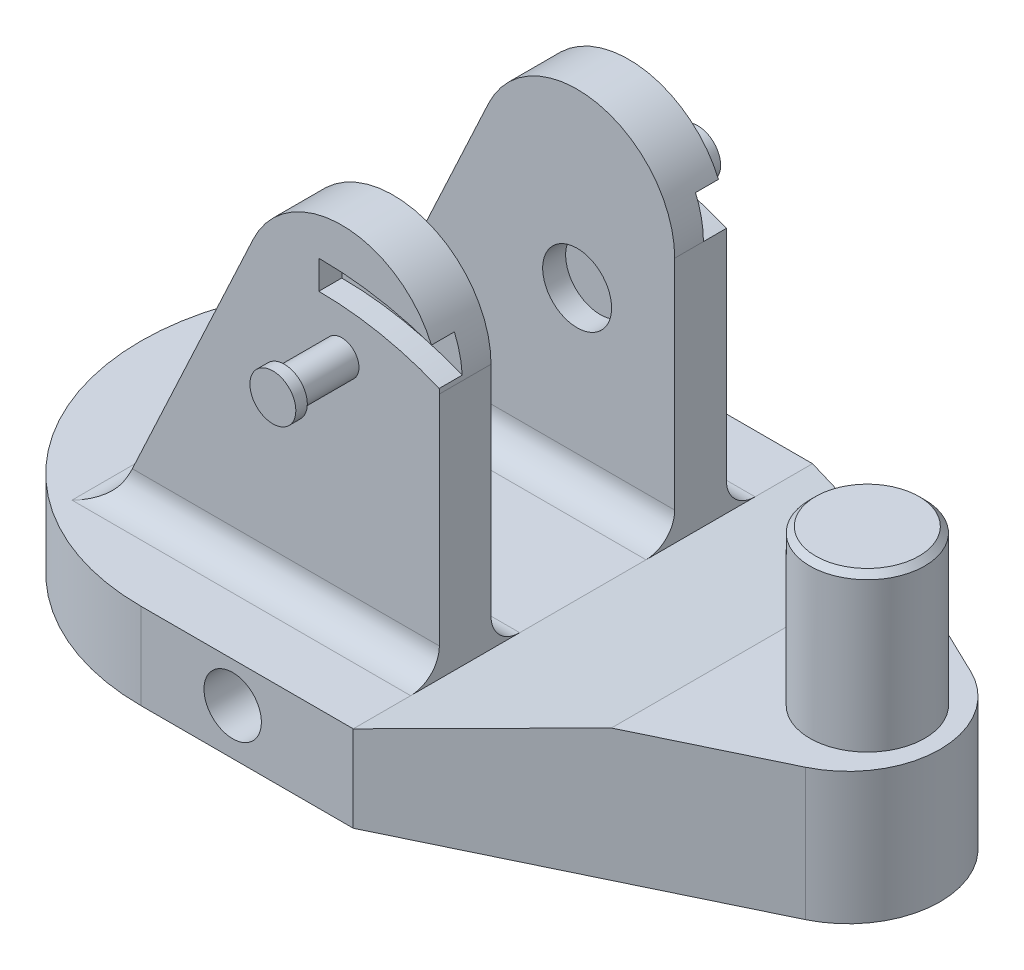
SolidWorks part; units mm, degrees
ref_plane "Płaszczyzna przednia" through (0, 0, 0) normal (0, 0, 1) x (1, 0, 0)
ref_plane "Płaszczyzna górna" through (0, 0, 0) normal (0, 1, 0) x (1, 0, 0)
ref_plane "Płaszczyzna prawa" through (0, 0, 0) normal (1, 0, 0) x (0, 0, -1)
sketch "Szkic5" plane through (0, 0, 0) normal (0, 1, 0) x (1, 0, 0)
  line L0 (0, 36.575) -> (0, -43.425) construction
  line L1 (0, -43.425) -> (37, -43.425)
  line L2 (37, -43.425) -> (37, 36.575)
  line L3 (37, 36.575) -> (0, 36.575)
  arc A0 (0, -43.425) -> (0, 36.575) centre (0, -3.425) cw
  dimension "D1" = 77
  dimension "D2" = 80
extrude "Dodanie-wyciągnięcie3" add sketch "Szkic5" along normal blind 15
sketch "Szkic7" plane through (0, 0, 0) normal (0, 1, 0) x (1, 0, 0)
  line L0 (0, 0) -> (37, 0) construction
  line L1 (37, -43.425) -> (90.1571, -17.8422)
  line L2 (37, 36.575) -> (90.1571, 10.9922)
  line L3 (0, -43.425) -> (37, -43.425) construction
  line L4 (37, -43.425) -> (37, 36.575) construction
  line L8 (0, -43.425) -> (37, -43.425)
  line L9 (37, -43.425) -> (37, 36.575)
  line L10 (37, 36.575) -> (0, 36.575)
  line L12 (37, -43.425) -> (37, 36.575)
  arc A0 (90.1571, 10.9922) -> (90.1571, -17.8422) centre (83.2185, -3.425) cw
  arc A2 (0, 36.575) -> (0, -43.425) centre (0, -3.425) ccw
  dimension "D2" = 16
  dimension "D3" = 0
  dimension "D1" = 25.7
extrude "Dodanie-wyciągnięcie4" add sketch "Szkic7" along normal blind 23
ref_plane "Płaszczyzna1" through (0, 0, 28.425) normal (0, 0, 1) x (1, 0, 0)
sketch "Szkic8" plane through (0, 0, 28.425) normal (0, 0, 1) x (1, 0, 0)
  line L0 (37, 15.0945) -> (37, 58)
  line L1 (4.5928, 65.1845) -> (-18.8087, 15)
  line L2 (0, 15) -> (37, 15) construction
  line L3 (0, 0) -> (37, 0) construction
  line L4 (0, 15) -> (-40, 15) construction
  line L5 (20, 58) -> (20, 81.5581) construction
  line L6 (20, 81.5581) -> (20, -13.5483) construction
  line L12 (0, 0) -> (37, 0)
  line L13 (37, 0) -> (37, 15)
  line L14 (37, 15) -> (0, 15)
  line L15 (0, 15) -> (0, 0)
  line L17 (37, 15.0945) -> (37, 15)
  line L18 (37, 15) -> (-18.8087, 15)
  arc A0 (37, 58) -> (4.5928, 65.1845) centre (20, 58) ccw
  dimension "D3" = 0
  dimension "D1" = 75
  dimension "D2" = 65
extrude "Dodanie-wyciągnięcie5" add sketch "Szkic8" against normal blind 9
ref_plane "Płaszczyzna4" through (0, 0, -21.575) normal (0, 0, 1) x (1, 0, 0)
sketch "Szkic23" plane through (0, 0, -21.575) normal (0, 0, 1) x (1, 0, 0)
  line L0 (37, 15) -> (37, 58)
  line L1 (37, 15) -> (-18.8087, 15)
  line L2 (-18.8087, 15) -> (4.5928, 65.1845)
  arc A0 (4.5928, 65.1845) -> (37, 58) centre (20, 58) cw
extrude "Dodanie-wyciągnięcie7" add sketch "Szkic23" along normal blind 9
sketch "Szkic24" plane through (0, 0, 28.425) normal (0, 0, 1) x (1, 0, 0)
  line L0 (37, 15) -> (67.3646, 23)
  line L1 (37, 23) -> (90.1571, 23) construction
  line L2 (67.3646, 23) -> (37, 23)
  line L3 (37, 23) -> (37, 15)
  dimension "D1" = 75.24
extrude "Wytnij-wyciągnięcie1" cut sketch "Szkic24" against normal through all both and the other way through all
sketch "Szkic26" plane through (0, 0, 19.425) normal (0, 0, -1) x (-1, 0, 0)
  line L0 (-37, 15) -> (-37, 58) construction
  line L1 (18.8087, 15) -> (-37, 15) construction
  circle A0 centre (-20, 45) radius 6
  dimension "D1" = 12
  dimension "D2" = 17
  dimension "D3" = 30
extrude "Wytnij-wyciągnięcie2" cut sketch "Szkic26" against normal blind 4
sketch "Szkic27" plane through (0, 0, -12.575) normal (0, 0, 1) x (1, 0, 0)
  line L0 (37, 15) -> (37, 58) construction
  line L1 (-18.8087, 15) -> (37, 15) construction
  circle A0 centre (20, 45) radius 6
  dimension "D1" = 12
  dimension "D2" = 17
  dimension "D3" = 30
extrude "Wytnij-wyciągnięcie3" cut sketch "Szkic27" against normal blind 4
sketch "Szkic28" plane through (0, 0, 43.425) normal (0, 0, 1) x (1, 0, 0)
  line L0 (0, 0) -> (37, 0) construction
  line L1 (-40, 15) -> (-40, 0) construction
  circle A0 centre (16, 8) radius 5
  dimension "D1" = 10
  dimension "D2" = 8
  dimension "D3" = 56
extrude "Wytnij-wyciągnięcie4" cut sketch "Szkic28" against normal through all
sketch "Szkic29" plane through (0, 23, 0) normal (0, 1, 0) x (1, 0, 0)
  circle A0 centre (86.22, -3.0978) radius 10
  arc A1 (0, 36.575) -> (0, -43.425) centre (0, -3.425) ccw construction
  arc A2 (90.1571, -17.8422) -> (90.1571, 10.9922) centre (83.2185, -3.425) ccw construction
  dimension "D1" = 20
  dimension "D2" = 126.22
extrude "Dodanie-wyciągnięcie8" add sketch "Szkic29" along normal blind 27
chamfer "Sfazowanie2" distance 1 angle 45 1 edges at (86.22, 50, 13.0978)
sketch "Szkic30" plane through (0, 0, -21.575) normal (0, 0, -1) x (-1, 0, 0)
  line L0 (-16, 8) -> (-16, 84.9488) construction
sketch "Szkic31" plane through (0, 0, 28.425) normal (0, 0, 1) x (1, 0, 0)
  line L0 (16, 8) -> (16, 84.9488) construction
  line L1 (37, 15) -> (37, 58) construction
  line L2 (-18.8087, 15) -> (37, 15) construction
  circle A0 centre (20, 55) radius 3
  dimension "D1" = 17
  dimension "D2" = 40
  dimension "D3" = 6
extrude "Dodanie-wyciągnięcie9" add sketch "Szkic31" along normal blind 10
sketch "Szkic32" plane through (0, 0, 38.425) normal (0, 0, 1) x (1, 0, 0)
  circle A0 centre (20, 55) radius 4
  dimension "D1" = 8
extrude "Dodanie-wyciągnięcie10" add sketch "Szkic32" along normal blind 2
sketch "Szkic33" plane through (0, 0, -21.575) normal (0, 0, -1) x (-1, 0, 0)
  line L0 (-37, 15) -> (-37, 58) construction
  line L1 (18.8087, 15) -> (-37, 15) construction
  circle A0 centre (-20, 55) radius 3
  dimension "D3" = 6
  dimension "D1" = 17
  dimension "D2" = 40
extrude "Dodanie-wyciągnięcie11" add sketch "Szkic33" along normal blind 10
sketch "Szkic34" plane through (0, 0, -31.575) normal (0, 0, -1) x (-1, 0, 0)
  circle A0 centre (-20, 55) radius 4
  dimension "D1" = 8
extrude "Dodanie-wyciągnięcie12" add sketch "Szkic34" along normal blind 2
fillet "Zaokrąglenie1" radius 5 1 edges at (-18.8087, 15, 23.925)
fillet "Zaokrąglenie2" radius 5 1 edges at (-18.8087, 15, -17.075)
fillet "Zaokrąglenie3" radius 5 1 edges at (7.503, 15, 28.425)
fillet "Zaokrąglenie4" radius 5 1 edges at (7.503, 15, 19.425)
fillet "Zaokrąglenie5" radius 5 1 edges at (7.503, 15, -12.575)
fillet "Zaokrąglenie6" radius 5 1 edges at (7.503, 15, -21.575)
sketch "Szkic36" plane through (0, 0, 28.425) normal (0, 0, 1) x (1, 0, 0)
  line L0 (16, 8) -> (16, 93.9312) construction
  line L1 (16, 68) -> (16, 63)
  arc A0 (36.9792, 58.8417) -> (16, 63) centre (16, 8) ccw
  arc A1 (35.624, 64.7001) -> (16, 68) centre (16, 8) ccw
  arc A2 (37, 58) -> (4.5928, 65.1845) centre (20, 58) ccw construction
  dimension "D1" = 55
  dimension "D2" = 60
extrude "Wytnij-wyciągnięcie5" cut sketch "Szkic36" against normal blind 4 and the other way through all
sketch "Szkic37" plane through (0, 0, -21.575) normal (0, 0, -1) x (-1, 0, 0)
  line L0 (-16, 8) -> (-16, 84.9488) construction
  line L1 (-16, 68) -> (-16, 62.231)
  arc A0 (-37, 58) -> (-16, 62.231) centre (-16, 8) cw
  arc A1 (-35.624, 64.7001) -> (-16, 68) centre (-16, 8) cw
  circle A2 centre (-16, 8) radius 5 construction
  circle A3 centre (-16, 8) radius 5
  arc M6 (-4.5928, 65.1845) -> (-37, 58) centre (-20, 58) ccw
  dimension "D1" = 54.231
  dimension "D2" = 60
extrude "Wytnij-wyciągnięcie6" cut sketch "Szkic37" against normal blind 4 contours A1 A0 L1 M6 region at (26.4057, 63.792, -21.575)
